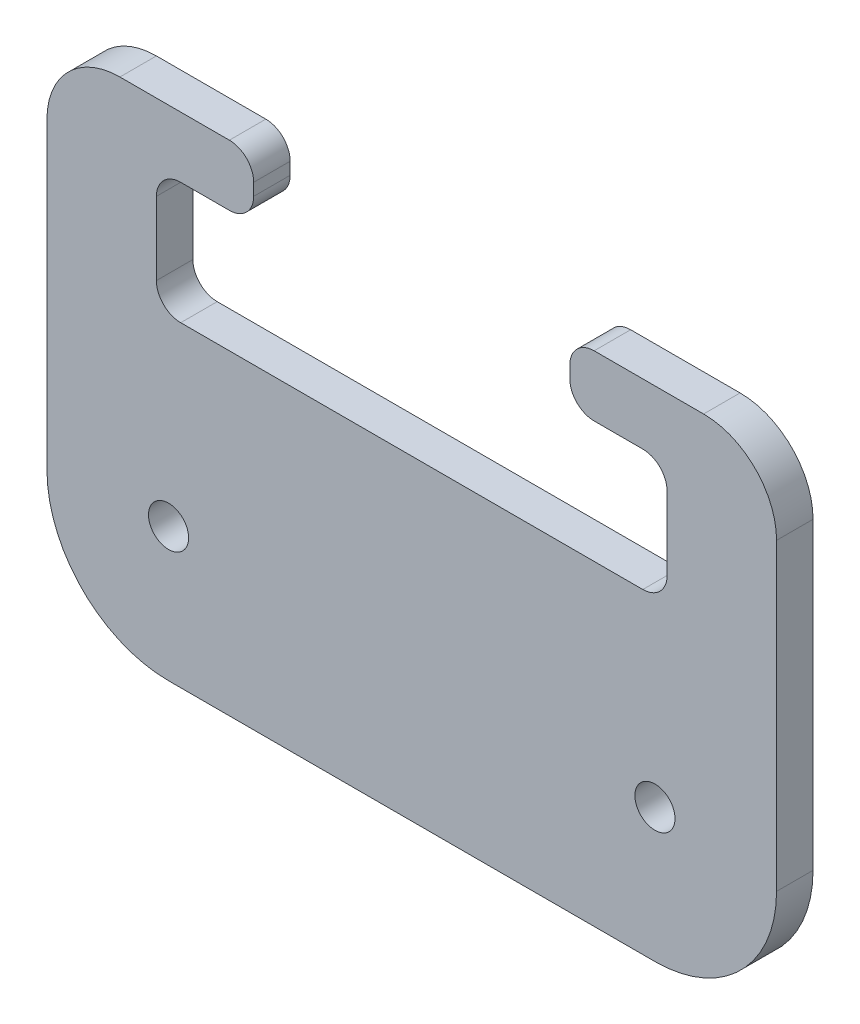
SolidWorks part; units mm, degrees
material "Thornel Mat VMA"
ref_plane "前视基准面" through (0, 0, 0) normal (0, 0, 1) x (1, 0, 0)
ref_plane "上视基准面" through (0, 0, 0) normal (0, 1, 0) x (1, 0, 0)
ref_plane "右视基准面" through (0, 0, 0) normal (1, 0, 0) x (0, 0, -1)
other "Configuration Table"
sketch "草图1" plane through (0, 0, 0) normal (0, 0, 1) x (1, 0, 0)
  line L0 (13, 22.5) -> (30, 22.5)
  line L1 (-30, 22.5) -> (-13, 22.5)
  line L2 (-30, 22.5) -> (-30, -22.5)
  line L3 (-30, -22.5) -> (30, -22.5)
  line L4 (30, 22.5) -> (30, -22.5)
  line L5 (-30, 22.5) -> (30, -22.5) construction
  line L6 (-30, -22.5) -> (30, 22.5) construction
  line L8 (13, 22.5) -> (13, 17.5)
  line L10 (-13, 22.5) -> (-13, 17.5)
  line L11 (21, 17.5) -> (13, 17.5)
  line L12 (21, 17.5) -> (21, 7.5)
  line L13 (21, 7.5) -> (-21, 7.5)
  line L14 (-21, 17.5) -> (-21, 7.5)
  line L15 (-13, 17.5) -> (-21, 17.5)
  point P0 (0, 0)
  dimension "D1" = 45
  dimension "D2" = 60
  dimension "D3" = 5
  dimension "D4" = 17
  dimension "D5" = 17
  dimension "D6" = 9
  dimension "D7" = 9
  dimension "D8" = 10
extrude "凸台-拉伸1" add sketch "草图1" along normal blind 3
fillet "圆角1" radius 6 2 edges at (30, 22.5, 1.5) (-30, 22.5, 1.5)
fillet "圆角2" radius 2 8 edges at (21, 17.5, 1.5) (21, 7.5, 1.5) (-21, 7.5, 1.5) (-21, 17.5, 1.5) (-13, 17.5, 1.5) (-13, 22.5, 1.5) (13, 17.5, 1.5) (13, 22.5, 1.5)
sketch "草图2" plane through (0, 0, 3) normal (0, 0, 1) x (1, 0, 0)
  line L0 (-30, -22.5) -> (30, -22.5) construction
  line L2 (0, 12.1144) -> (0, -26.36) construction
  circle A0 centre (-20, -7.5) radius 1.65
  circle A1 centre (20, -7.5) radius 1.65
  dimension "D1" = 3.3
  dimension "D2" = 3.3
  dimension "D6" = 20
  dimension "D3" = 15
  dimension "D4" = 15
  dimension "D5" = 40
extrude "切除-拉伸1" cut sketch "草图2" against normal blind 5
fillet "圆角3" radius 10 2 edges at (-30, -22.5, 1.5) (30, -22.5, 1.5)
sketch "草图3" plane through (0, 0, 3) normal (0, 0, 1) x (1, 0, 0)
  line L0 (-20, -22.5) -> (20, -22.5) construction
  line L1 (-30, -22.5) -> (30, -22.5)
  line L2 (-30, -22.5) -> (-30, -18.5)
  line L3 (-30, -18.5) -> (30, -18.5)
  line L4 (30, -22.5) -> (30, -18.5)
  line L5 (30, -12.5) -> (30, 16.5) construction
  line L6 (-30, 16.5) -> (-30, -12.5) construction
  dimension "D1" = 4
extrude "切除-拉伸2" cut sketch "草图3" against normal blind 10
fillet "圆角4" radius 10 2 edges at (28, -18.5, 1.5) (-28, -18.5, 1.5)
